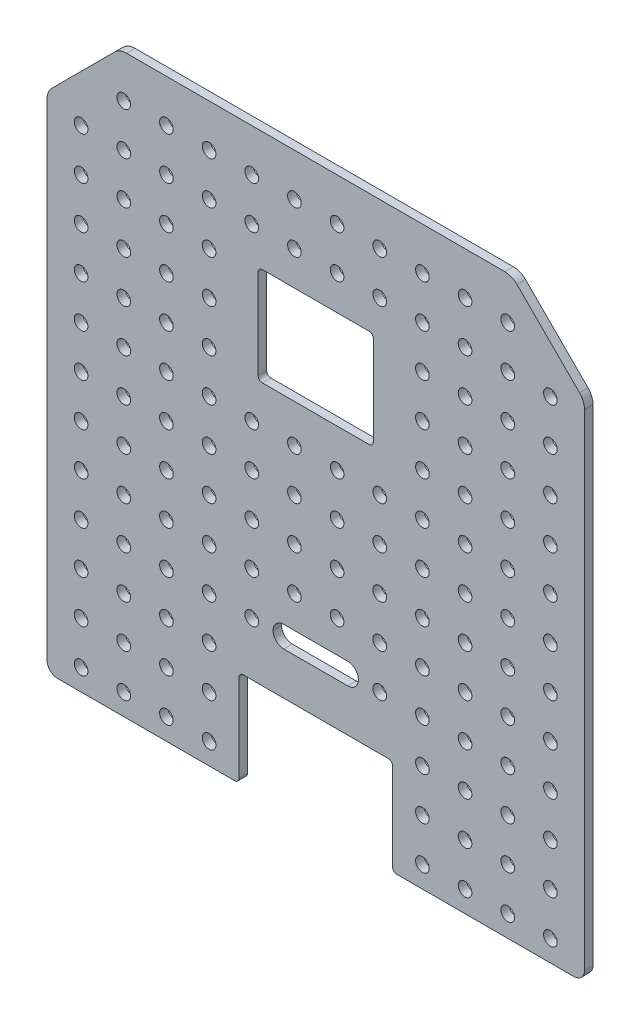
SolidWorks part; units mm, degrees
ref_plane "Front" through (0, 0, 0) normal (0, 0, 1) x (1, 0, 0)
ref_plane "Top" through (0, 0, 0) normal (0, 1, 0) x (1, 0, 0)
ref_plane "Right" through (0, 0, 0) normal (1, 0, 0) x (0, 0, -1)
sketch "Эскиз1" plane through (0, 0, 0) normal (0, 0, 1) x (1, 0, 0)
  line L0 (-63, 0) -> (63, 0)
  line L1 (63, 0) -> (63, -135)
  line L3 (63, -135) -> (-63, -135)
  line L5 (-63, -135) -> (-63, 0)
  point P3 (0, 0)
  point P7 (0, -135)
  dimension "D1" = 126
  dimension "D2" = 135
extrude "Основа" add sketch "Эскиз1" along normal blind 2
sketch "Эскиз3" plane through (0, 0, 0) normal (0, 0, -1) x (-1, 0, 0)
  line L0 (63, -135) -> (-63, -135) construction
  line L2 (-13.5, -28) -> (-13.5, -51)
  line L3 (-13.5, -51) -> (13.5, -51)
  line L4 (13.5, -28) -> (13.5, -51)
  line L7 (13.5, -28) -> (-13.5, -28)
  point P4 (0, -28)
  point P10 (0, -51)
  dimension "D1" = 23
  dimension "D2" = 27
  dimension "D3" = 84
extrude "Окошко для доступа к шилду" cut sketch "Эскиз3" against normal through all
sketch "Эскиз4" plane through (0, 0, 0) normal (0, 0, -1) x (-1, 0, 0)
  line L0 (63, -135) -> (-63, -135) construction
  line L1 (-18, -112.5) -> (18, -112.5)
  line L2 (-18, -112.5) -> (-18, -135)
  line L3 (-18, -135) -> (18, -135)
  line L4 (18, -112.5) -> (18, -135)
  point P6 (0, -135)
  dimension "D1" = 22.5
  dimension "D2" = 36
extrude "Под объектив камеры" cut sketch "Эскиз4" against normal through all
chamfer "Фаска1" distance 17 1 edges at (-63, 0, 1)
chamfer "Фаска2" distance 17 1 edges at (63, 0, 1)
sketch "Эскиз2" plane through (0, 0, 0) normal (0, 0, -1) x (-1, 0, 0)
  line L0 (0, 0) -> (0, -135) construction
  line L1 (63, -135) -> (18, -135) construction
  line L2 (-18, -135) -> (-63, -135) construction
  circle A0 centre (5, -130) radius 1.6 construction
  circle A1 centre (15, -130) radius 1.6 construction
  circle A2 centre (25, -130) radius 1.6
  circle A3 centre (35, -130) radius 1.6
  circle A4 centre (45, -130) radius 1.6
  circle A5 centre (55, -130) radius 1.6
  circle A6 centre (65, -130) radius 1.6
  circle A7 centre (75, -130) radius 1.6 construction
  circle A8 centre (-75, -130) radius 1.6 construction
  circle A9 centre (-65, -130) radius 1.6
  circle A10 centre (-55, -130) radius 1.6
  circle A11 centre (-45, -130) radius 1.6
  circle A12 centre (-35, -130) radius 1.6
  circle A13 centre (-25, -130) radius 1.6
  circle A14 centre (-15, -130) radius 1.6 construction
  circle A15 centre (-5, -130) radius 1.6 construction
  circle A16 centre (5, -120) radius 1.6 construction
  circle A17 centre (15, -120) radius 1.6 construction
  circle A18 centre (25, -120) radius 1.6
  circle A19 centre (35, -120) radius 1.6
  circle A20 centre (45, -120) radius 1.6
  circle A21 centre (55, -120) radius 1.6
  circle A22 centre (65, -120) radius 1.6
  circle A23 centre (75, -120) radius 1.6 construction
  circle A24 centre (-75, -120) radius 1.6 construction
  circle A25 centre (-65, -120) radius 1.6
  circle A26 centre (-55, -120) radius 1.6
  circle A27 centre (-45, -120) radius 1.6
  circle A28 centre (-35, -120) radius 1.6
  circle A29 centre (-25, -120) radius 1.6
  circle A30 centre (-15, -120) radius 1.6 construction
  circle A31 centre (-5, -120) radius 1.6 construction
  circle A32 centre (5, -110) radius 1.6 construction
  circle A33 centre (15, -110) radius 1.6 construction
  circle A34 centre (25, -110) radius 1.6
  circle A35 centre (35, -110) radius 1.6
  circle A36 centre (45, -110) radius 1.6
  circle A37 centre (55, -110) radius 1.6
  circle A38 centre (65, -110) radius 1.6
  circle A39 centre (75, -110) radius 1.6 construction
  circle A40 centre (-75, -110) radius 1.6 construction
  circle A41 centre (-65, -110) radius 1.6
  circle A42 centre (-55, -110) radius 1.6
  circle A43 centre (-45, -110) radius 1.6
  circle A44 centre (-35, -110) radius 1.6
  circle A45 centre (-25, -110) radius 1.6
  circle A46 centre (-15, -110) radius 1.6 construction
  circle A47 centre (-5, -110) radius 1.6 construction
  circle A48 centre (5, -100) radius 1.6
  circle A49 centre (15, -100) radius 1.6
  circle A50 centre (25, -100) radius 1.6
  circle A51 centre (35, -100) radius 1.6
  circle A52 centre (45, -100) radius 1.6
  circle A53 centre (55, -100) radius 1.6
  circle A54 centre (65, -100) radius 1.6
  circle A55 centre (75, -100) radius 1.6 construction
  circle A56 centre (-75, -100) radius 1.6 construction
  circle A57 centre (-65, -100) radius 1.6
  circle A58 centre (-55, -100) radius 1.6
  circle A59 centre (-45, -100) radius 1.6
  circle A60 centre (-35, -100) radius 1.6
  circle A61 centre (-25, -100) radius 1.6
  circle A62 centre (-15, -100) radius 1.6
  circle A63 centre (-5, -100) radius 1.6
  circle A64 centre (5, -90) radius 1.6
  circle A65 centre (15, -90) radius 1.6
  circle A66 centre (25, -90) radius 1.6
  circle A67 centre (35, -90) radius 1.6
  circle A68 centre (45, -90) radius 1.6
  circle A69 centre (55, -90) radius 1.6
  circle A70 centre (65, -90) radius 1.6
  circle A71 centre (75, -90) radius 1.6 construction
  circle A72 centre (-75, -90) radius 1.6 construction
  circle A73 centre (-65, -90) radius 1.6
  circle A74 centre (-55, -90) radius 1.6
  circle A75 centre (-45, -90) radius 1.6
  circle A76 centre (-35, -90) radius 1.6
  circle A77 centre (-25, -90) radius 1.6
  circle A78 centre (-15, -90) radius 1.6
  circle A79 centre (-5, -90) radius 1.6
  circle A80 centre (5, -80) radius 1.6
  circle A81 centre (15, -80) radius 1.6
  circle A82 centre (25, -80) radius 1.6
  circle A83 centre (35, -80) radius 1.6
  circle A84 centre (45, -80) radius 1.6
  circle A85 centre (55, -80) radius 1.6
  circle A86 centre (65, -80) radius 1.6
  circle A87 centre (75, -80) radius 1.6 construction
  circle A88 centre (-75, -80) radius 1.6 construction
  circle A89 centre (-65, -80) radius 1.6
  circle A90 centre (-55, -80) radius 1.6
  circle A91 centre (-45, -80) radius 1.6
  circle A92 centre (-35, -80) radius 1.6
  circle A93 centre (-25, -80) radius 1.6
  circle A94 centre (-15, -80) radius 1.6
  circle A95 centre (-5, -80) radius 1.6
  circle A96 centre (5, -70) radius 1.6
  circle A97 centre (15, -70) radius 1.6
  circle A98 centre (25, -70) radius 1.6
  circle A99 centre (35, -70) radius 1.6
  circle A100 centre (45, -70) radius 1.6
  circle A101 centre (55, -70) radius 1.6
  circle A102 centre (65, -70) radius 1.6
  circle A103 centre (75, -70) radius 1.6 construction
  circle A104 centre (-75, -70) radius 1.6 construction
  circle A105 centre (-65, -70) radius 1.6
  circle A106 centre (-55, -70) radius 1.6
  circle A107 centre (-45, -70) radius 1.6
  circle A108 centre (-35, -70) radius 1.6
  circle A109 centre (-25, -70) radius 1.6
  circle A110 centre (-15, -70) radius 1.6
  circle A111 centre (-5, -70) radius 1.6
  circle A112 centre (5, -60) radius 1.6
  circle A113 centre (15, -60) radius 1.6
  circle A114 centre (25, -60) radius 1.6
  circle A115 centre (35, -60) radius 1.6
  circle A116 centre (45, -60) radius 1.6
  circle A117 centre (55, -60) radius 1.6
  circle A118 centre (65, -60) radius 1.6
  circle A119 centre (75, -60) radius 1.6 construction
  circle A120 centre (-75, -60) radius 1.6 construction
  circle A121 centre (-65, -60) radius 1.6
  circle A122 centre (-55, -60) radius 1.6
  circle A123 centre (-45, -60) radius 1.6
  circle A124 centre (-35, -60) radius 1.6
  circle A125 centre (-25, -60) radius 1.6
  circle A126 centre (-15, -60) radius 1.6
  circle A127 centre (-5, -60) radius 1.6
  circle A128 centre (5, -50) radius 1.6 construction
  circle A129 centre (15, -50) radius 1.6 construction
  circle A130 centre (25, -50) radius 1.6
  circle A131 centre (35, -50) radius 1.6
  circle A132 centre (45, -50) radius 1.6
  circle A133 centre (55, -50) radius 1.6
  circle A134 centre (65, -50) radius 1.6
  circle A135 centre (75, -50) radius 1.6 construction
  circle A136 centre (-75, -50) radius 1.6 construction
  circle A137 centre (-65, -50) radius 1.6
  circle A138 centre (-55, -50) radius 1.6
  circle A139 centre (-45, -50) radius 1.6
  circle A140 centre (-35, -50) radius 1.6
  circle A141 centre (-25, -50) radius 1.6
  circle A142 centre (-15, -50) radius 1.6 construction
  circle A143 centre (-5, -50) radius 1.6 construction
  circle A144 centre (5, -40) radius 1.6 construction
  circle A145 centre (15, -40) radius 1.6 construction
  circle A146 centre (25, -40) radius 1.6
  circle A147 centre (35, -40) radius 1.6
  circle A148 centre (45, -40) radius 1.6
  circle A149 centre (55, -40) radius 1.6
  circle A150 centre (65, -40) radius 1.6
  circle A151 centre (75, -40) radius 1.6 construction
  circle A152 centre (-75, -40) radius 1.6 construction
  circle A153 centre (-65, -40) radius 1.6
  circle A154 centre (-55, -40) radius 1.6
  circle A155 centre (-45, -40) radius 1.6
  circle A156 centre (-35, -40) radius 1.6
  circle A157 centre (-25, -40) radius 1.6
  circle A158 centre (-15, -40) radius 1.6 construction
  circle A159 centre (-5, -40) radius 1.6 construction
  circle A160 centre (5, -30) radius 1.6 construction
  circle A161 centre (15, -30) radius 1.6 construction
  circle A162 centre (25, -30) radius 1.6
  circle A163 centre (35, -30) radius 1.6
  circle A164 centre (45, -30) radius 1.6
  circle A165 centre (55, -30) radius 1.6
  circle A166 centre (65, -30) radius 1.6 construction
  circle A167 centre (75, -30) radius 1.6 construction
  circle A168 centre (-75, -30) radius 1.6 construction
  circle A169 centre (-65, -30) radius 1.6 construction
  circle A170 centre (-55, -30) radius 1.6
  circle A171 centre (-45, -30) radius 1.6
  circle A172 centre (-35, -30) radius 1.6
  circle A173 centre (-25, -30) radius 1.6
  circle A174 centre (-15, -30) radius 1.6 construction
  circle A175 centre (-5, -30) radius 1.6 construction
  circle A176 centre (5, -20) radius 1.6
  circle A177 centre (15, -20) radius 1.6
  circle A178 centre (25, -20) radius 1.6
  circle A179 centre (35, -20) radius 1.6
  circle A180 centre (45, -20) radius 1.6
  circle A181 centre (55, -20) radius 1.6
  circle A182 centre (65, -20) radius 1.6 construction
  circle A183 centre (75, -20) radius 1.6 construction
  circle A184 centre (-75, -20) radius 1.6 construction
  circle A185 centre (-65, -20) radius 1.6 construction
  circle A186 centre (-55, -20) radius 1.6
  circle A187 centre (-45, -20) radius 1.6
  circle A188 centre (-35, -20) radius 1.6
  circle A189 centre (-25, -20) radius 1.6
  circle A190 centre (-15, -20) radius 1.6
  circle A191 centre (-5, -20) radius 1.6
  circle A192 centre (5, -10) radius 1.6
  circle A193 centre (15, -10) radius 1.6
  circle A194 centre (25, -10) radius 1.6
  circle A195 centre (35, -10) radius 1.6
  circle A196 centre (45, -10) radius 1.6
  circle A197 centre (55, -10) radius 1.6 construction
  circle A198 centre (65, -10) radius 1.6 construction
  circle A199 centre (75, -10) radius 1.6 construction
  circle A200 centre (-75, -10) radius 1.6 construction
  circle A201 centre (-65, -10) radius 1.6 construction
  circle A202 centre (-55, -10) radius 1.6 construction
  circle A203 centre (-45, -10) radius 1.6
  circle A204 centre (-35, -10) radius 1.6
  circle A205 centre (-25, -10) radius 1.6
  circle A206 centre (-15, -10) radius 1.6
  circle A207 centre (-5, -10) radius 1.6
  circle A208 centre (5, 0) radius 1.6 construction
  circle A209 centre (15, 0) radius 1.6 construction
  circle A210 centre (25, 0) radius 1.6 construction
  circle A211 centre (35, 0) radius 1.6 construction
  circle A212 centre (45, 0) radius 1.6 construction
  circle A213 centre (55, 0) radius 1.6 construction
  circle A214 centre (65, 0) radius 1.6 construction
  circle A215 centre (75, 0) radius 1.6 construction
  circle A216 centre (-75, 0) radius 1.6 construction
  circle A217 centre (-65, 0) radius 1.6 construction
  circle A218 centre (-55, 0) radius 1.6 construction
  circle A219 centre (-45, 0) radius 1.6 construction
  circle A220 centre (-35, 0) radius 1.6 construction
  circle A221 centre (-25, 0) radius 1.6 construction
  circle A222 centre (-15, 0) radius 1.6 construction
  circle A223 centre (-5, 0) radius 1.6 construction
  circle A224 centre (5, 10) radius 1.6 construction
  circle A225 centre (15, 10) radius 1.6 construction
  circle A226 centre (25, 10) radius 1.6 construction
  circle A227 centre (35, 10) radius 1.6 construction
  circle A228 centre (45, 10) radius 1.6 construction
  circle A229 centre (55, 10) radius 1.6 construction
  circle A230 centre (65, 10) radius 1.6 construction
  circle A231 centre (75, 10) radius 1.6 construction
  circle A232 centre (-75, 10) radius 1.6 construction
  circle A233 centre (-65, 10) radius 1.6 construction
  circle A234 centre (-55, 10) radius 1.6 construction
  circle A235 centre (-45, 10) radius 1.6 construction
  circle A236 centre (-35, 10) radius 1.6 construction
  circle A237 centre (-25, 10) radius 1.6 construction
  circle A238 centre (-15, 10) radius 1.6 construction
  circle A239 centre (-5, 10) radius 1.6 construction
  circle A240 centre (5, 20) radius 1.6 construction
  circle A241 centre (15, 20) radius 1.6 construction
  circle A242 centre (25, 20) radius 1.6 construction
  circle A243 centre (35, 20) radius 1.6 construction
  circle A244 centre (45, 20) radius 1.6 construction
  circle A245 centre (55, 20) radius 1.6 construction
  circle A246 centre (65, 20) radius 1.6 construction
  circle A247 centre (75, 20) radius 1.6 construction
  circle A248 centre (-75, 20) radius 1.6 construction
  circle A249 centre (-65, 20) radius 1.6 construction
  circle A250 centre (-55, 20) radius 1.6 construction
  circle A251 centre (-45, 20) radius 1.6 construction
  circle A252 centre (-35, 20) radius 1.6 construction
  circle A253 centre (-25, 20) radius 1.6 construction
  circle A254 centre (-15, 20) radius 1.6 construction
  circle A255 centre (-5, 20) radius 1.6 construction
  circle A256 centre (5, 30) radius 1.6 construction
  circle A257 centre (15, 30) radius 1.6 construction
  circle A258 centre (25, 30) radius 1.6 construction
  circle A259 centre (35, 30) radius 1.6 construction
  circle A260 centre (45, 30) radius 1.6 construction
  circle A261 centre (55, 30) radius 1.6 construction
  circle A262 centre (65, 30) radius 1.6 construction
  circle A263 centre (75, 30) radius 1.6 construction
  circle A264 centre (-75, 30) radius 1.6 construction
  circle A265 centre (-65, 30) radius 1.6 construction
  circle A266 centre (-55, 30) radius 1.6 construction
  circle A267 centre (-45, 30) radius 1.6 construction
  circle A268 centre (-35, 30) radius 1.6 construction
  circle A269 centre (-25, 30) radius 1.6 construction
  circle A270 centre (-15, 30) radius 1.6 construction
  circle A271 centre (-5, 30) radius 1.6 construction
  circle A272 centre (5, 40) radius 1.6 construction
  circle A273 centre (15, 40) radius 1.6 construction
  circle A274 centre (25, 40) radius 1.6 construction
  circle A275 centre (35, 40) radius 1.6 construction
  circle A276 centre (45, 40) radius 1.6 construction
  circle A277 centre (55, 40) radius 1.6 construction
  circle A278 centre (65, 40) radius 1.6 construction
  circle A279 centre (75, 40) radius 1.6 construction
  circle A280 centre (-75, 40) radius 1.6 construction
  circle A281 centre (-65, 40) radius 1.6 construction
  circle A282 centre (-55, 40) radius 1.6 construction
  circle A283 centre (-45, 40) radius 1.6 construction
  circle A284 centre (-35, 40) radius 1.6 construction
  circle A285 centre (-25, 40) radius 1.6 construction
  circle A286 centre (-15, 40) radius 1.6 construction
  circle A287 centre (-5, 40) radius 1.6 construction
  circle A288 centre (5, 50) radius 1.6 construction
  circle A289 centre (15, 50) radius 1.6 construction
  circle A290 centre (25, 50) radius 1.6 construction
  circle A291 centre (35, 50) radius 1.6 construction
  circle A292 centre (45, 50) radius 1.6 construction
  circle A293 centre (55, 50) radius 1.6 construction
  circle A294 centre (65, 50) radius 1.6 construction
  circle A295 centre (75, 50) radius 1.6 construction
  circle A296 centre (-75, 50) radius 1.6 construction
  circle A297 centre (-65, 50) radius 1.6 construction
  circle A298 centre (-55, 50) radius 1.6 construction
  circle A299 centre (-45, 50) radius 1.6 construction
  circle A300 centre (-35, 50) radius 1.6 construction
  circle A301 centre (-25, 50) radius 1.6 construction
  circle A302 centre (-15, 50) radius 1.6 construction
  circle A303 centre (-5, 50) radius 1.6 construction
  circle A304 centre (5, 60) radius 1.6 construction
  circle A305 centre (15, 60) radius 1.6 construction
  circle A306 centre (25, 60) radius 1.6 construction
  circle A307 centre (35, 60) radius 1.6 construction
  circle A308 centre (45, 60) radius 1.6 construction
  circle A309 centre (55, 60) radius 1.6 construction
  circle A310 centre (65, 60) radius 1.6 construction
  circle A311 centre (75, 60) radius 1.6 construction
  circle A312 centre (-75, 60) radius 1.6 construction
  circle A313 centre (-65, 60) radius 1.6 construction
  circle A314 centre (-55, 60) radius 1.6 construction
  circle A315 centre (-45, 60) radius 1.6 construction
  circle A316 centre (-35, 60) radius 1.6 construction
  circle A317 centre (-25, 60) radius 1.6 construction
  circle A318 centre (-15, 60) radius 1.6 construction
  circle A319 centre (-5, 60) radius 1.6 construction
  dimension "D1" = 3.2
  dimension "D2" = 5
  dimension "D3" = 5
  dimension "D5" = 10
  dimension "D7" = 10
  dimension "D4" = 8
  dimension "D6" = 20
extrude "Сетка отв 10х10мм" cut sketch "Эскиз2" against normal through all
fillet "Скругление1" radius 1 8 edges at (-13.5, -51, 1) (13.5, -51, 1) (13.5, -28, 1) (-13.5, -28, 1) (18, -112.5, 1) (-18, -112.5, 1) (18, -135, 1) (-18, -135, 1)
fillet "Скругление3" radius 2.5 2 edges at (-63, -135, 1) (63, -135, 1)
fillet "Скругление2" radius 4 4 edges at (63, -17, 1) (-63, -17, 1) (46, 0, 1) (-46, 0, 1)
sketch "Эскиз5" plane through (0, 0, 2) normal (0, 0, 1) x (1, 0, 0)
  line L0 (19, -135) -> (60.5, -135) construction
  line L1 (-10, -97.5) -> (10, -97.5)
  line L2 (-10, -97.5) -> (-10, -102.5)
  line L3 (-10, -102.5) -> (10, -102.5)
  line L4 (10, -97.5) -> (10, -102.5)
  point P4 (0, -102.5)
  point P8 (10, -100)
  dimension "D1" = 5
  dimension "D2" = 20
  dimension "D3" = 35
extrude "Под шлейф камеры" cut sketch "Эскиз5" against normal through all
fillet "Скругление4" radius 2.5 4 edges at (10, -102.5, 1) (10, -97.5, 1) (-10, -102.5, 1) (-10, -97.5, 1)
